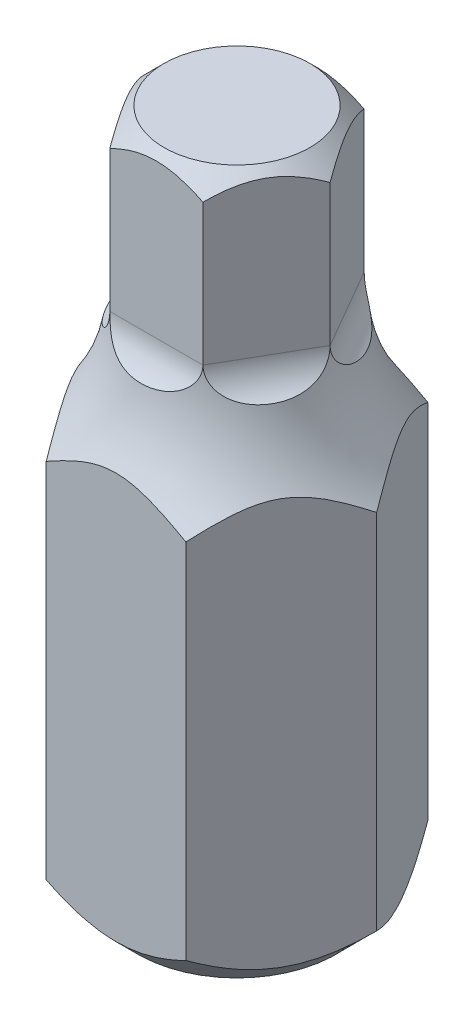
SolidWorks part; units mm, degrees
ref_plane "Front Plane" through (0, 0, 0) normal (0, 0, 1) x (1, 0, 0)
ref_plane "Top Plane" through (0, 0, 0) normal (0, 1, 0) x (1, 0, 0)
ref_plane "Right Plane" through (0, 0, 0) normal (1, 0, 0) x (0, 0, -1)
sketch "Sketch1" plane through (0, 0, 0) normal (0, 1, 0) x (1, 0, 0)
  line L1 (1.7321, 3) -> (-1.7321, 3)
  line L2 (-1.7321, 3) -> (-3.4641, 0)
  line L3 (-3.4641, 0) -> (-1.7321, -3)
  line L4 (-1.7321, -3) -> (1.7321, -3)
  line L5 (1.7321, -3) -> (3.4641, 0)
  line L6 (3.4641, 0) -> (1.7321, 3)
  circle A0 centre (0, 0) radius 3 construction
  point P1 (0, 3)
  dimension "D1" = 6
extrude "Boss-Extrude1" add sketch "Sketch1" along normal blind 12
sketch "Sketch2" plane through (0, 12, 0) normal (0, 1, 0) x (1, 0, 0)
  line L1 (1.1547, 2) -> (-1.1547, 2)
  line L2 (-1.1547, 2) -> (-2.3094, 0)
  line L3 (-2.3094, 0) -> (-1.1547, -2)
  line L4 (-1.1547, -2) -> (1.1547, -2)
  line L5 (1.1547, -2) -> (2.3094, 0)
  line L6 (2.3094, 0) -> (1.1547, 2)
  circle A0 centre (0, 0) radius 2 construction
  point P1 (0, 2)
  dimension "D1" = 4
extrude "Boss-Extrude2" add sketch "Sketch2" along normal blind 5
fillet "Fillet1" radius 1 6 edges at (1.7321, 12, -1) (0, 12, -2) (-1.7321, 12, -1) (-1.7321, 12, 1) (1.7321, 12, 1) (0, 12, 2)
sketch "Sketch3" plane through (0, 0, 0) normal (0, 0, 1) x (1, 0, 0)
  line L0 (1.8094, 17) -> (2.3094, 16.5)
  line L1 (1.1547, 17) -> (2.3094, 17) construction
  line L2 (2.3094, 17) -> (2.3094, 13) construction
  line L3 (2.3094, 16.5) -> (2.3094, 17)
  line L4 (2.3094, 17) -> (1.8094, 17)
  line L5 (2.4641, 0) -> (3.4641, 1)
  line L6 (1.7321, 0) -> (3.4641, 0) construction
  line L7 (3.4641, 12) -> (3.4641, 0) construction
  line L8 (3.4641, 1) -> (3.4641, 0)
  line L9 (3.4641, 0) -> (2.4641, 0)
  line L10 (0, 0) -> (0, 1.643) construction
  circle A0 centre (6.8094, 13) radius 4.5
  dimension "D3" = 9
  dimension "D1" = 0.5
  dimension "D2" = 45
  dimension "D4" = 45
  dimension "D5" = 1
revolve "Cut-Revolve1" cut sketch "Sketch3" angle 360 about L10
